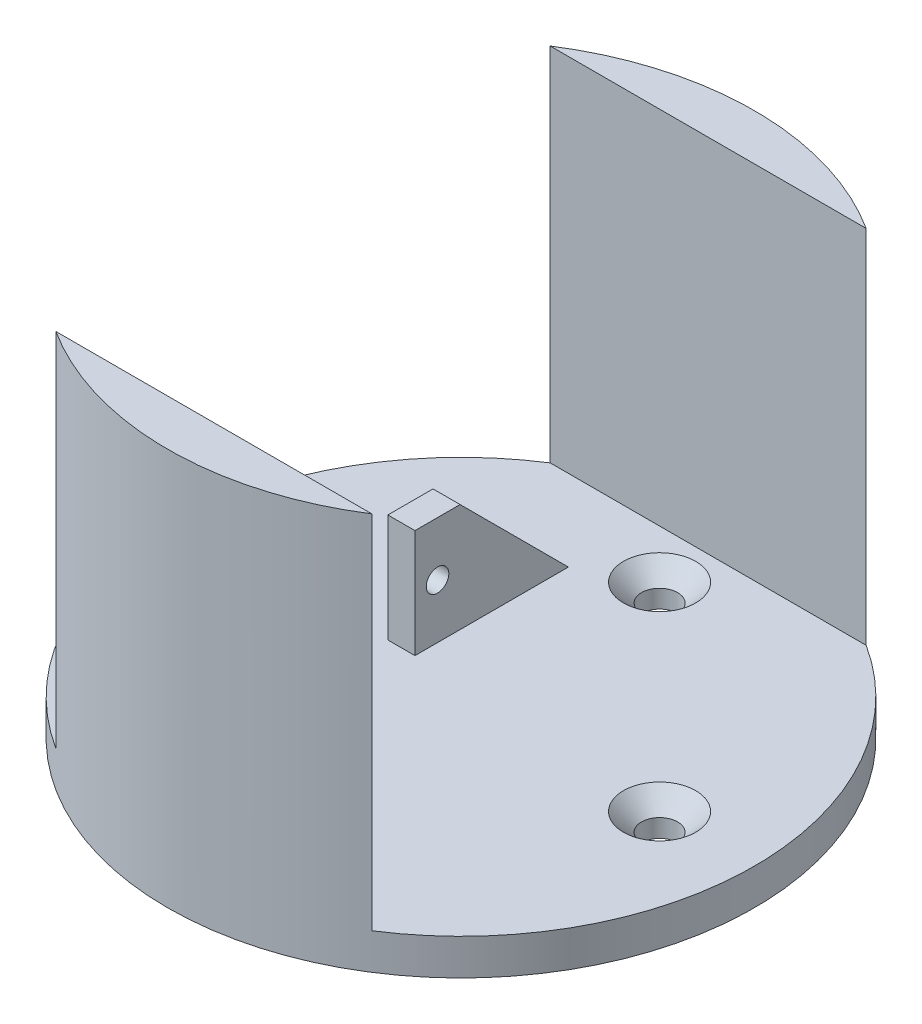
SolidWorks part; units mm, degrees
ref_plane "Front Plane" through (0, 0, 0) normal (0, 0, 1) x (1, 0, 0)
ref_plane "Top Plane" through (0, 0, 0) normal (0, 1, 0) x (1, 0, 0)
ref_plane "Right Plane" through (0, 0, 0) normal (1, 0, 0) x (0, 0, -1)
sketch "Sketch1" plane through (0, 0, 0) normal (0, 1, 0) x (1, 0, 0)
  circle A0 centre (0, 0) radius 32.5
  circle A1 centre (-22, 0) radius 2
  circle A2 centre (0, 22) radius 2
  circle A3 centre (22, 0) radius 2
  circle A4 centre (0, -22) radius 2
  point P14 (0, 0)
  dimension "D1" = 65
  dimension "D2" = 4
  dimension "D3" = 22
  dimension "D4" = 4
extrude "Boss-Extrude1" add sketch "Sketch1" along normal blind 4
sketch "Sketch2" plane through (0, 4, 0) normal (0, 1, 0) x (1, 0, 0)
  line L0 (17.5, 27.3861) -> (-17.5, 27.3861)
  line L1 (0, 0) -> (-10.9128, 0) construction
  line L2 (17.5, -27.3861) -> (-17.5, -27.3861)
  arc A0 (17.5, 27.3861) -> (-17.5, 27.3861) centre (0, 0) ccw
  arc A1 (17.5, -27.3861) -> (-17.5, -27.3861) centre (0, 0) cw
  circle A4 centre (0, 0) radius 32.5 construction
  dimension "D1" = 35
extrude "Boss-Extrude2" add sketch "Sketch2" along normal blind 40
chamfer "Chamfer1" distance 2 angle 45 4 edges at (0, 4, 24) (0, 4, -20) (22, 4, 2) (-22, 4, 2)
sketch "Sketch3" plane through (0, 4, 0) normal (0, 1, 0) x (1, 0, 0)
  line L0 (0, 0) -> (-7.2128, 0) construction
  line L1 (-9.5, 6.4) -> (-6.5, 6.4)
  line L2 (-9.5, 6.4) -> (-9.5, 1.4)
  line L3 (-9.5, 1.4) -> (-6.5, 1.4)
  line L4 (-6.5, 6.4) -> (-6.5, 1.4)
  line L5 (-9.5, 6.4) -> (-6.5, 1.4) construction
  line L6 (-9.5, 1.4) -> (-6.5, 6.4) construction
  line L8 (-6.5, -26.4) -> (-9.5, -26.4)
  line L9 (-6.5, -26.4) -> (-6.5, -21.4)
  line L10 (-6.5, -21.4) -> (-9.5, -21.4)
  line L11 (-9.5, -26.4) -> (-9.5, -21.4)
  line L12 (-6.5, -26.4) -> (-9.5, -21.4) construction
  line L13 (-6.5, -21.4) -> (-9.5, -26.4) construction
  point P0 (-8, 3.9)
  point P5 (-8, -23.9)
  point P13 (0, 0)
  dimension "D3" = 5
  dimension "D4" = 3.9
  dimension "D1" = 8
  dimension "D2" = 3
  dimension "D5" = 27.8
  dimension "D6" = 3
  dimension "D7" = 5
extrude "Boss-Extrude3" add sketch "Sketch3" along normal blind 12
sketch "Sketch4" plane through (-9.5, 0, 0) normal (-1, 0, 0) x (0, 0, 1)
  line L0 (-6.4, 4) -> (-1.4, 4) construction
  line L1 (-6.4, 16) -> (-1.4, 16) construction
  line L2 (21.4, 16) -> (26.4, 16) construction
  circle A0 centre (-3.9, 10) radius 1.25
  circle A1 centre (23.9, 10) radius 1.25
  point P6 (-3.9, 16)
  point P11 (23.9, 16)
  point P12 (0, 0)
  dimension "D1" = 2.5
  dimension "D3" = 2.5
  dimension "D2" = 6
extrude "Cut-Extrude1" cut sketch "Sketch4" against normal up to surface (3 mm away) up to face at (-6.5, 10, -3.9)
sketch "Sketch5" plane through (0, 4, 0) normal (0, 1, 0) x (1, 0, 0)
  line L0 (-30.95, 1.9) -> (-30.95, -3.1)
  line L1 (-26.95, 1.9) -> (-26.95, -3.1)
  line L2 (-30.95, 1.9) -> (-26.95, -3.1) construction
  line L3 (-30.95, -3.1) -> (-26.95, 1.9) construction
  line L4 (-9.5, 6.4) -> (-9.5, 1.4) construction
  line L5 (-9.5, 1.4) -> (-6.5, 1.4) construction
  arc A0 (-30.95, 1.9) -> (-26.95, 1.9) centre (-28.95, 1.9) cw
  arc A1 (-30.95, -3.1) -> (-26.95, -3.1) centre (-28.95, -3.1) ccw
  point P6 (-28.95, -0.6)
  dimension "D1" = 4
  dimension "D2" = 5
  dimension "D3" = 19.45
  dimension "D4" = 2
extrude "Cut-Extrude2" cut sketch "Sketch5" against normal blind 3
chamfer "Chamfer3" distance 12 angle 45 2 edges at (-8, 4, -6.4) (-8, 4, 26.4)
equation "\"D3@Sketch4\"=\"D1@Sketch4\""
equation "\"D7@Sketch3\"=\"D3@Sketch3\""
equation "\"D6@Sketch3\"=\"D2@Sketch3\""
